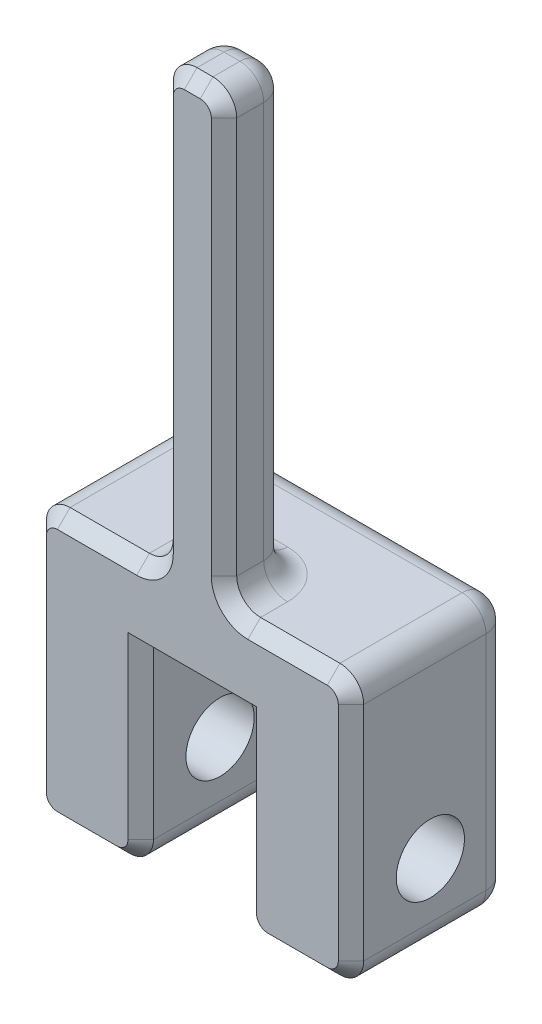
SolidWorks part; units mm, degrees
ref_plane "Front Plane" through (0, 0, 0) normal (0, 0, 1) x (1, 0, 0)
ref_plane "Top Plane" through (0, 0, 0) normal (0, 1, 0) x (1, 0, 0)
ref_plane "Right Plane" through (0, 0, 0) normal (1, 0, 0) x (0, 0, -1)
sketch "Sketch1" plane through (0, 0, 0) normal (0, 1, 0) x (1, 0, 0)
  line L1 (-10, -5) -> (10, -5)
  line L2 (-10, -5) -> (-10, 5)
  line L3 (-10, 5) -> (10, 5)
  line L4 (10, -5) -> (10, 5)
  line L5 (-10, -5) -> (10, 5) construction
  line L6 (-10, 5) -> (10, -5) construction
  point P0 (0, 0)
  dimension "D1" = 10
  dimension "D2" = 20
extrude "Boss-Extrude1" add sketch "Sketch1" along normal blind 10
sketch "Sketch2" plane through (10, 0, 0) normal (1, 0, 0) x (0, 0, -1)
  line L0 (-5, 10) -> (5, 0) construction
  circle A0 centre (0, 5) radius 2.15
  dimension "D1" = 4.3
extrude "Cut-Extrude1" cut sketch "Sketch2" against normal through all
sketch "Sketch3" plane through (0, 10, 0) normal (0, 1, 0) x (1, 0, 0)
  line L0 (-10, -5) -> (10, -5) construction
  line L1 (-2, -5) -> (2, -5)
  line L2 (-2, -5) -> (-2, -1)
  line L3 (-2, -1) -> (2, -1)
  line L4 (2, -5) -> (2, -1)
  line L5 (-2, -5) -> (2, -1) construction
  line L6 (-2, -1) -> (2, -5) construction
  line L7 (-10, 5) -> (-10, -5) construction
  line L8 (10, -5) -> (10, 5) construction
  point P4 (0, -3)
  dimension "D1" = 8
  dimension "D2" = 8
  dimension "D3" = 4
extrude "Boss-Extrude2" add sketch "Sketch3" along normal blind 35
sketch "Sketch4" plane through (10, 0, 0) normal (1, 0, 0) x (0, 0, -1)
  line L0 (5, 10) -> (5, 0) construction
  line L1 (-5, 10) -> (5, 10)
  line L2 (-5, 10) -> (-5, 17)
  line L3 (-5, 17) -> (5, 17)
  line L4 (5, 10) -> (5, 17)
  line L5 (-5, 10) -> (5, 17) construction
  line L6 (-5, 17) -> (5, 10) construction
  point P4 (0, 13.5)
  dimension "D1" = 7
extrude "Boss-Extrude3" add sketch "Sketch4" against normal up to surface (20 mm away) up to face at (-10, 5, -2.15)
sketch "Sketch5" plane through (0, 0, 0) normal (0, -1, 0) x (1, 0, 0)
  line L0 (-10, 5) -> (10, 5) construction
  line L1 (3.25, -5) -> (-3.25, -5)
  line L2 (3.25, -5) -> (3.25, 5)
  line L3 (3.25, 5) -> (-3.25, 5)
  line L4 (-3.25, -5) -> (-3.25, 5)
  line L5 (3.25, -5) -> (-3.25, 5) construction
  line L6 (3.25, 5) -> (-3.25, -5) construction
  line L7 (-10, -5) -> (-10, 5) construction
  point P0 (0, 0)
  dimension "D1" = 6.75
extrude "Cut-Extrude2" cut sketch "Sketch5" against normal blind 12
fillet "Fillet1" radius 1.5 22 edges at (-2, 17, 3) (2, 17, 3) (0, 45, 1) (-2, 31, 1) (0, 17, 1) (2, 31, 1) (3.25, 6, -5) (6.625, 0, -5) (10, 8.5, -5) (0, 17, -5) (-10, 8.5, -5) (-6.625, 0, -5) (-3.25, 6, -5) (0, 12, -5) (2, 45, 3) (-2, 45, 3) (-3.25, 0, 0) (3.25, 0, 0) (10, 0, 0) (-10, 0, 0) (10, 17, 0) (-10, 17, 0)
chamfer "Chamfer1" distance 0.8 angle 45 22 edges at (2.4393, 17.4393, 5) (6, 17, 5) (9.5607, 16.5607, 5) (10, 8.5, 5) (9.5607, 0.4393, 5) (6.625, 0, 5) (3.6893, 0.4393, 5) (3.25, 6.75, 5) (0, 12, 5) (-3.25, 6.75, 5) (-3.6893, 0.4393, 5) (-6.625, 0, 5) (-9.5607, 0.4393, 5) (-10, 8.5, 5) (-9.5607, 16.5607, 5) (-6, 17, 5) (-2.4393, 17.4393, 5) (-2, 31, 5) (-1.5607, 44.5607, 5) (0, 45, 5) (1.5607, 44.5607, 5) (2, 31, 5)
